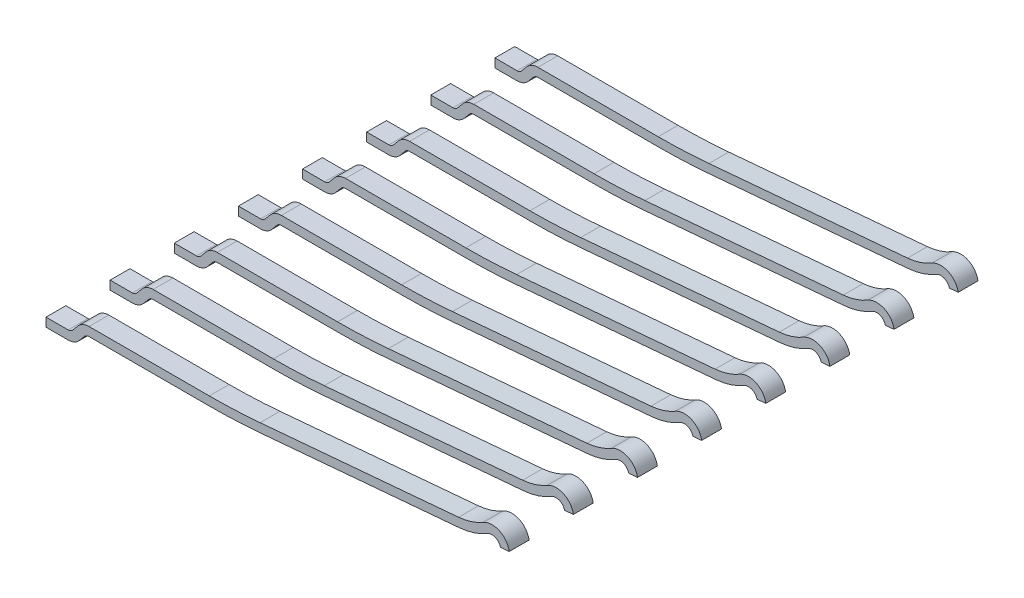
SolidWorks part; units mm, degrees
ref_plane "Płaszczyzna przednia" through (0, 0, 0) normal (0, 0, 1) x (1, 0, 0)
ref_plane "Płaszczyzna górna" through (0, 0, 0) normal (0, 1, 0) x (1, 0, 0)
ref_plane "Płaszczyzna prawa" through (0, 0, 0) normal (1, 0, 0) x (0, 0, -1)
sketch "Sketch1" plane through (0, 0, 0) normal (0, 0, 1) x (1, 0, 0)
  line L0 (-3.4274, -0.1555) -> (-3.5154, -0.2604)
  line L1 (-3.592, -0.2962) -> (-3.973, -0.2962)
  line L2 (-3.973, -0.2962) -> (-3.973, -0.4462)
  line L3 (-3.973, -0.4462) -> (-3.592, -0.4462)
  line L4 (-3.4005, -0.3569) -> (-3.3124, -0.2519)
  line L5 (-3.2358, -0.2162) -> (-1.1725, -0.2162)
  line L6 (-0.2878, -0.1775) -> (3.1169, 0.1203)
  line L7 (3.8227, 0.1821) -> (3.973, 0.1952)
  line L8 (3.1038, 0.2698) -> (-0.3009, -0.0281)
  line L9 (-1.1725, -0.0662) -> (-3.2358, -0.0662)
  arc A0 (-3.592, -0.2962) -> (-3.5154, -0.2604) centre (-3.592, -0.1962) ccw
  arc A1 (-3.592, -0.4462) -> (-3.4005, -0.3569) centre (-3.592, -0.1962) ccw
  arc A2 (-3.2358, -0.2162) -> (-3.3124, -0.2519) centre (-3.2358, -0.3162) ccw
  arc A3 (-1.1725, -0.2162) -> (-0.2878, -0.1775) centre (-1.1725, 9.9338) ccw
  arc A4 (3.1169, 0.1203) -> (3.6008, 0.2754) centre (3.0167, 1.266) ccw
  arc A5 (3.8227, 0.1821) -> (3.6008, 0.2754) centre (3.677, 0.1462) ccw
  arc A6 (3.973, 0.1952) -> (3.5246, 0.4046) centre (3.677, 0.1462) ccw
  arc A7 (3.1038, 0.2698) -> (3.5246, 0.4046) centre (3.0167, 1.266) ccw
  arc A8 (-1.1725, -0.0662) -> (-0.3009, -0.0281) centre (-1.1725, 9.9338) ccw
  arc A9 (-3.2358, -0.0662) -> (-3.4274, -0.1555) centre (-3.2358, -0.3162) ccw
extrude "Boss-Extrude1" add sketch "Sketch1" along normal blind 0.34
pattern_linear "LPattern1" count 8 spacing 1.1 along (0, 0, -1) of bodies 101
